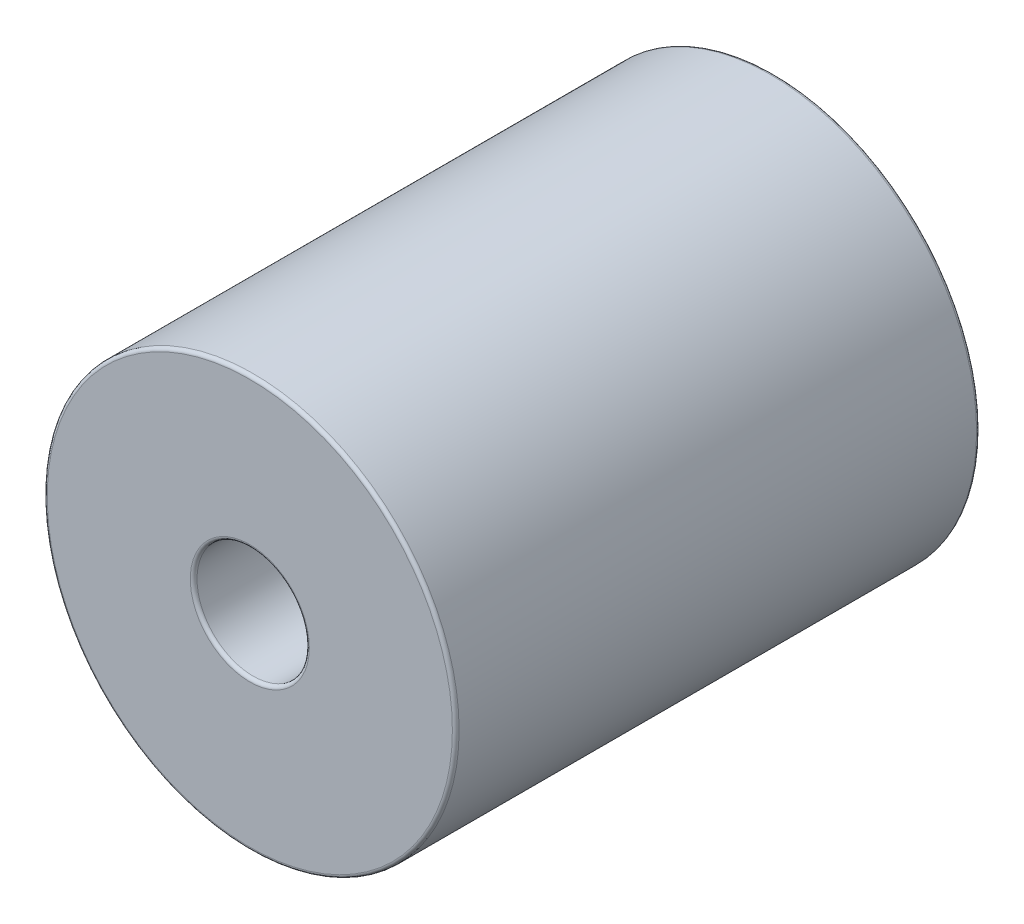
SolidWorks part; units mm, degrees
ref_plane "Front" through (0, 0, 0) normal (0, 0, 1) x (1, 0, 0)
ref_plane "Top" through (0, 0, 0) normal (0, 1, 0) x (1, 0, 0)
ref_plane "Right" through (0, 0, 0) normal (1, 0, 0) x (0, 0, -1)
sketch "Sketch1" plane through (0, 0, 0) normal (0, 0, 1) x (1, 0, 0)
  line L0 (0, 0.5953) -> (0, -0.5953) construction
  line L1 (0, 2.1828) -> (0, -2.1828) construction
  line L2 (0, 1.9844) -> (0, -1.9844) construction
  circle A0 centre (0, 0) radius 1.9844 construction
  circle A1 centre (0, 0) radius 2.1828 construction
  dimension "od" = 4.3656
  dimension "compressed od" = 3.9688
  dimension "for wire rope dia" = 1.1906
sketch "Sketch2" plane through (0, 0, 0) normal (1, 0, 0) x (0, 0, -1)
  line L0 (-2.7781, 0) -> (2.7781, 0) construction
  dimension "sleeve lg" = 5.5562
sketch "Sketch3" plane through (0, 0, 0) normal (0, 0, 1) x (1, 0, 0)
  circle A0 centre (0, 0) radius 2.1828
  circle A1 centre (0, 0) radius 0.5953
extrude "Boss-Extrude1" add sketch "Sketch3" along normal up to vertex (2.7781 mm away) and the other way up to vertex (2.7781 mm away) up to point (0, 0, 2.7781) other way up to point (0, 0, -2.7781)
fillet "Fillet1" radius 0.0357 4 edges at (2.1828, 0, -2.7781) (2.1828, 0, 2.7781) (0.5953, 0, 2.7781) (0.5953, 0, -2.7781)
equation "\"D1@Fillet1\"=\"for wire rope dia@Sketch1\"*.03"
